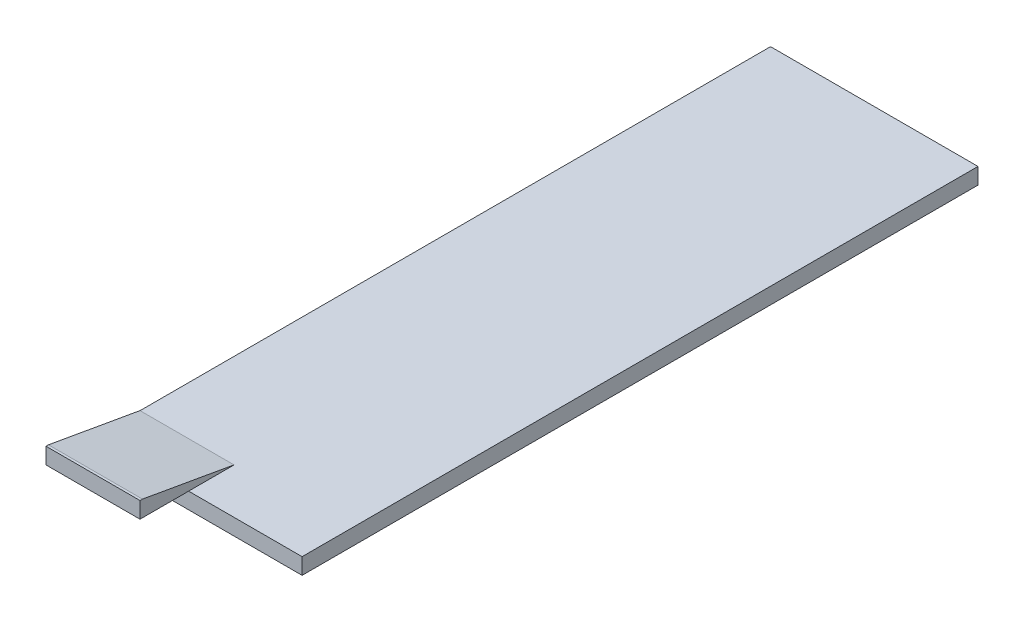
SolidWorks part; units mm, degrees
ref_plane "Front Plane" through (0, 0, 0) normal (0, 0, 1) x (1, 0, 0)
ref_plane "Top Plane" through (0, 0, 0) normal (0, 1, 0) x (1, 0, 0)
ref_plane "Right Plane" through (0, 0, 0) normal (1, 0, 0) x (0, 0, -1)
sketch "Sketch1" plane through (0, 0, 0) normal (0, 1, 0) x (1, 0, 0)
  line L1 (0, 0) -> (25.6, 0)
  line L2 (0, 0) -> (0, 83.4)
  line L3 (0, 83.4) -> (25.6, 83.4)
  line L4 (25.6, 0) -> (25.6, 83.4)
  dimension "D1" = 83.4
  dimension "D2" = 25.6
extrude "Boss-Extrude1" add sketch "Sketch1" along normal blind 2
sketch "Sketch2" plane through (0, 2, 0) normal (0, 1, 0) x (1, 0, 0)
  line L0 (0, 83.4) -> (0, 0) construction
  line L1 (0, 5.6) -> (11.6, 5.6)
  line L2 (0, 5.6) -> (0, -6)
  line L3 (0, -6) -> (11.6, -6)
  line L4 (11.6, 5.6) -> (11.6, -6)
  line L6 (0, 0) -> (25.6, 0) construction
  dimension "D1" = 11.6
  dimension "D2" = 6
  dimension "D3" = 5.6
extrude "Boss-Extrude2" add sketch "Sketch2" along normal blind 2
chamfer "Chamfer1" distance 11.3 angle 10 1 edges at (5.8, 4, -5.6) first distance on face at (5.8, 4, 0.2)
